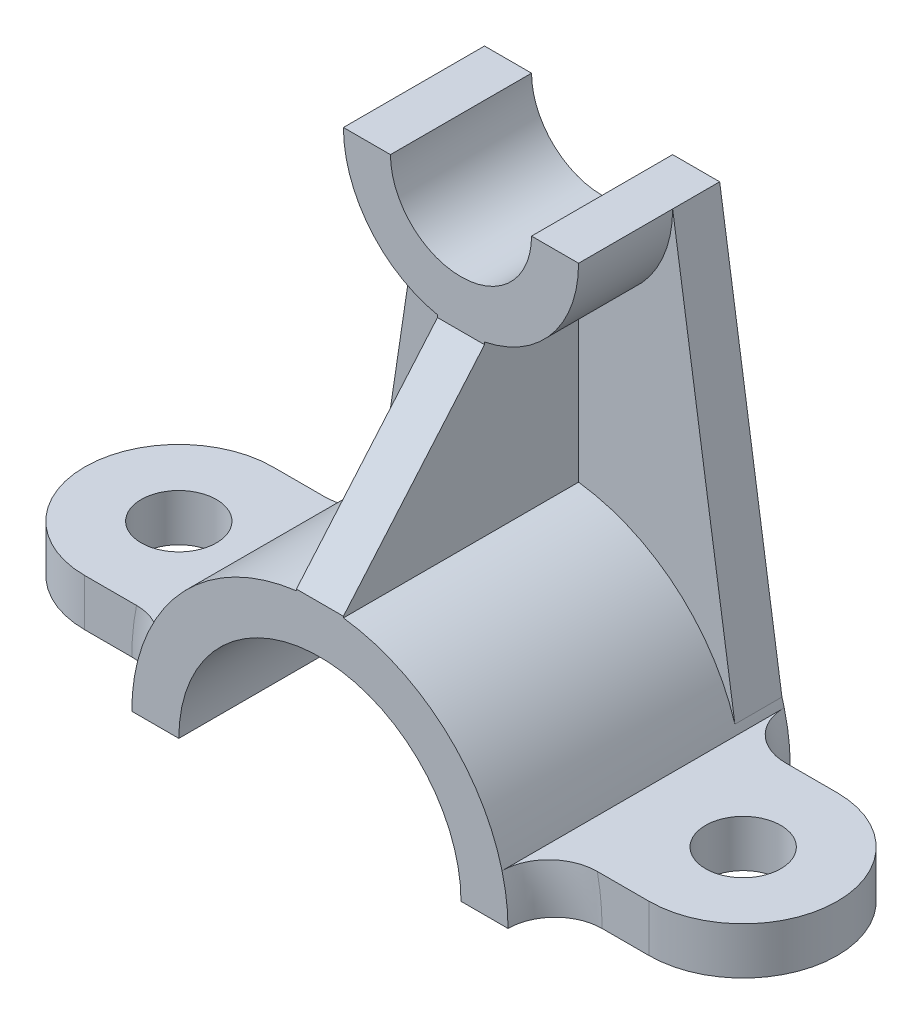
SolidWorks part; units mm, degrees
ref_plane "Front Plane" through (0, 0, 0) normal (0, 0, 1) x (1, 0, 0)
ref_plane "Top Plane" through (0, 0, 0) normal (0, 1, 0) x (1, 0, 0)
ref_plane "Right Plane" through (0, 0, 0) normal (1, 0, 0) x (0, 0, -1)
sketch "Sketch1" plane through (0, 0, 0) normal (0, 0, 1) x (1, 0, 0)
  line L0 (-60, 0) -> (60, 0) construction
  line L1 (60, 0) -> (-60, 0) construction
  line L2 (-40, 0) -> (-30, 0)
  line L3 (30, 0) -> (40, 0)
  line L4 (30, 0) -> (30, 10)
  line L5 (30, 0) -> (60, 0)
  line L6 (30, 10) -> (60, 10)
  line L7 (60, 0) -> (60, 10)
  line L8 (0, 0) -> (0, 100) construction
  line L9 (-30, 0) -> (-30, 10)
  line L10 (-60, 0) -> (-60, 10)
  line L11 (-30, 10) -> (-60, 10)
  line L12 (-30, 0) -> (-60, 0)
  arc A0 (30, 0) -> (-30, 0) centre (0, 0) ccw
  arc A1 (40, 0) -> (-40, 0) centre (0, 0) ccw
  dimension "D2" = 80
  dimension "D1" = 120
  dimension "D4" = 30
  dimension "D5" = 10
  dimension "D6" = 100
extrude "Boss-Extrude1" add sketch "Sketch1" against normal blind 40 from offset 10 contours A1 L5 L7 L6 | L9 L11 L10 L12 region at (49.7862, 5.0517, 0) offset against normal yes
extrude "Extrude-Thin1" add sketch "Sketch1<3>" against normal blind 60 thin contours A0 thin type one direction wall 10
sketch "Sketch1<3>" plane through (0, 0, 0) normal (0, 0, 1) x (1, 0, 0) same geometry as "Sketch1"
sketch "Sketch2" plane through (0, 0, -60) normal (0, 0, -1) x (-1, 0, 0)
  line L0 (0, 0) -> (0, 100) construction
  line L1 (0, 0) -> (0, 100) construction
  line L2 (-40, 0) -> (-30, 0)
  line L3 (30, 0) -> (40, 0)
  line L4 (-40, 0) -> (-30, 0)
  line L5 (30, 0) -> (40, 0)
  line L6 (-25, 100) -> (-15, 100)
  line L7 (15, 100) -> (25, 100)
  line L8 (40, 0) -> (25, 100)
  line L9 (-40, 0) -> (-25, 100)
  arc A0 (-25, 100) -> (25, 100) centre (0, 100) ccw
  arc A1 (-15, 100) -> (15, 100) centre (0, 100) ccw
  arc A2 (40, 0) -> (-40, 0) centre (0, 0) ccw
  arc A3 (30, 0) -> (-30, 0) centre (0, 0) ccw
  arc A4 (40, 0) -> (-40, 0) centre (0, 0) ccw
  arc A5 (30, 0) -> (-30, 0) centre (0, 0) ccw
  arc M5 (40, 0) -> (-40, 0) centre (0, 0) ccw
  dimension "D2" = 50
  dimension "D3" = 30
  dimension "D1" = 0
extrude "Boss-Extrude2" add sketch "Sketch2" against normal blind 30 separate body contours A0 L1 A1 L6 | L1 A0 L7 A1 region at (12.9977, 87.0023, -60) region at (-12.9977, 87.0023, -60)
extrude "Boss-Extrude3" add sketch "Sketch2<5>" against normal blind 10 contours A4 L1 A0 L9 | L1 L8 A0 M5 region at (18.1581, 56.3138, -60) region at (-18.1581, 56.3138, -60)
sketch "Sketch2<5>" plane through (0, 0, -60) normal (0, 0, -1) x (-1, 0, 0) same geometry as "Sketch2"
fillet "Fillet2" radius 10 4 edges at (39.6812, 5.0402, -50) (-39.6812, 5.0402, -50) (-39.6812, 5.0402, -10) (39.6812, 5.0402, -10)
sketch "Sketch3" plane through (0, 0, 0) normal (1, 0, 0) x (0, 0, -1)
  line L0 (30, 75) -> (0, 40)
  line L1 (0, 40) -> (0, 37.743)
  line L2 (0, 37.743) -> (50.3628, 37.743)
  line L3 (50.3628, 37.743) -> (50.3628, 76.3548)
  line L4 (50.3628, 76.3548) -> (30, 76.3548)
  line L5 (30, 76.3548) -> (30, 75)
extrude "Boss-Extrude4" add sketch "Sketch3" along normal mid plane 10
sketch "Sketch4" plane through (0, 10, 0) normal (0, 1, 0) x (1, 0, 0)
  line L0 (60, 50) -> (60, 10) construction
  line L1 (60, 50) -> (60, 38)
  line L2 (60, 22) -> (60, 10)
  arc A0 (60, 10) -> (60, 50) centre (60, 30) ccw
  circle A1 centre (60, 30) radius 8
  line M5 (60, 10) -> (60, 50)
  dimension "D1" = 16
extrude "Cut-Extrude1" cut sketch "Sketch4" against normal through all contours A1 M5 | A1 M5 region at (56.6047, 10, -30) region at (63.3953, 10, -30)
extrude "Boss-Extrude6" add sketch "Sketch4<7>" against normal blind 10 contours A1 A0 M5 region at (69.4584, 10, -30)
sketch "Sketch4<7>" plane through (0, 10, 0) normal (0, 1, 0) x (1, 0, 0) same geometry as "Sketch4"
mirror "Mirror1" about plane through (0, 0, 0) normal (1, 0, 0) of "Cut-Extrude1", "Boss-Extrude6"
